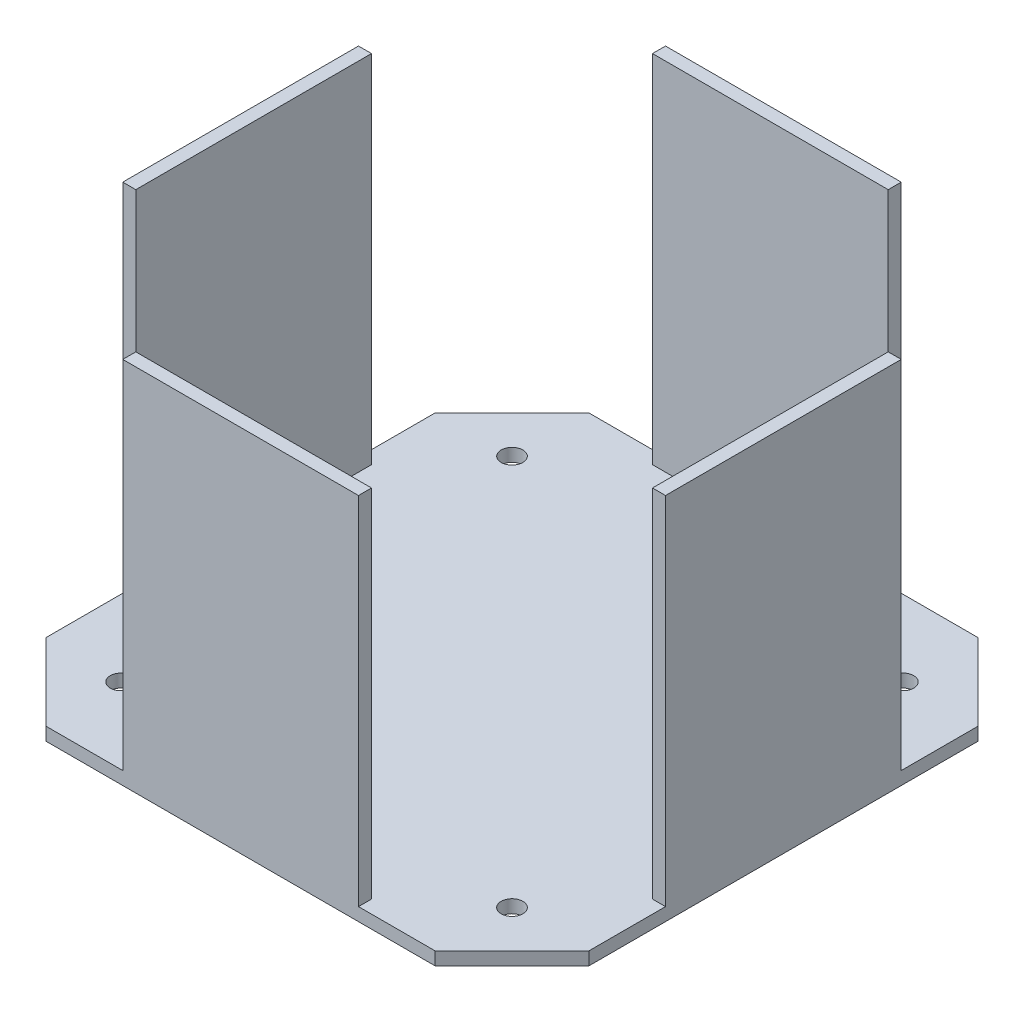
SolidWorks part; units mm, degrees
ref_plane "Front Plane" through (0, 0, 0) normal (0, 0, 1) x (1, 0, 0)
ref_plane "Top Plane" through (0, 0, 0) normal (0, 1, 0) x (1, 0, 0)
ref_plane "Right Plane" through (0, 0, 0) normal (1, 0, 0) x (0, 0, -1)
sketch "Sketch2" plane through (0, 0, 0) normal (0, 1, 0) x (1, 0, 0)
  line L1 (62.5, -62.5) -> (-62.5, -62.5)
  line L2 (62.5, -62.5) -> (62.5, 62.5)
  line L3 (62.5, 62.5) -> (-62.5, 62.5)
  line L4 (-62.5, -62.5) -> (-62.5, 62.5)
  line L5 (62.5, -62.5) -> (-62.5, 62.5) construction
  line L6 (62.5, 62.5) -> (-62.5, -62.5) construction
  point P0 (0, 0)
  dimension "D1" = 125
  dimension "D2" = 125
extrude "Boss-Extrude1" add sketch "Sketch2" along normal blind 85
shell "Shell1" thickness 3 removed face at (0, 85, 0)
sketch "Sketch3" plane through (0, 85, 0) normal (0, 1, 0) x (1, 0, 0)
  line L0 (27.1447, -62.5) -> (62.5, -27.1447) construction
  line L1 (-62.5, -62.5) -> (62.5, -62.5) construction
  line L2 (62.5, -62.5) -> (62.5, 62.5) construction
  line L3 (27.1447, -62.5) -> (62.5, -62.5)
  line L4 (62.5, -62.5) -> (62.5, -27.1447)
  line L5 (27.1447, -62.5) -> (27.1447, -59.5)
  line L6 (-59.5, -59.5) -> (59.5, -59.5) construction
  line L8 (-27.1447, -59.5) -> (-30.1447, -59.5)
  line L9 (62.5, -27.1447) -> (59.5, -27.1447)
  line L10 (59.5, -59.5) -> (59.5, 59.5) construction
  line L11 (59.5, -27.1447) -> (59.5, -30.1447)
  line L13 (59.5, -30.1447) -> (59.5, -59.5)
  line L14 (59.5, -59.5) -> (27.1447, -59.5)
  line L15 (-27.1447, -62.5) -> (-27.1447, -59.5)
  line L16 (-62.5, -62.5) -> (-27.1447, -62.5)
  line L17 (-62.5, -27.1447) -> (-62.5, -62.5)
  line L18 (-62.5, -27.1447) -> (-59.5, -27.1447)
  line L19 (-59.5, -59.5) -> (-59.5, -27.1447)
  line L20 (-30.1447, -59.5) -> (-59.5, -59.5)
  line L21 (-59.5, 27.1447) -> (-59.5, 30.1447)
  line L22 (-62.5, 27.1447) -> (-59.5, 27.1447)
  line L23 (-62.5, 62.5) -> (-62.5, 27.1447)
  line L24 (-27.1447, 62.5) -> (-62.5, 62.5)
  line L25 (-27.1447, 62.5) -> (-27.1447, 59.5)
  line L26 (-59.5, 59.5) -> (-27.1447, 59.5)
  line L27 (-59.5, 30.1447) -> (-59.5, 59.5)
  line L28 (27.1447, 59.5) -> (30.1447, 59.5)
  line L29 (27.1447, 62.5) -> (27.1447, 59.5)
  line L30 (62.5, 62.5) -> (27.1447, 62.5)
  line L31 (62.5, 27.1447) -> (62.5, 62.5)
  line L32 (62.5, 27.1447) -> (59.5, 27.1447)
  line L34 (30.1447, 59.5) -> (59.5, 59.5)
  line L35 (59.5, 59.5) -> (59.5, 27.1447) [skipped]
  line L36 (59.5, 59.5) -> (59.5, 27.1447)
  point P41 (0, 0)
  dimension "D1" = 50
  dimension "D2" = 45
  dimension "D3" = 4
extrude "Cut-Extrude1" cut sketch "Sketch3" against normal up to surface (82 mm away) up to face at (0, 3, 0)
sketch "Sketch4" plane through (0, 3, 0) normal (0, 1, 0) x (1, 0, 0)
  line L0 (-62.5, -44.8223) -> (-62.5, -62.5)
  line L1 (-62.5, -62.5) -> (-62.5, -27.1447) construction
  line L2 (-62.5, -62.5) -> (-44.8223, -62.5)
  line L3 (-27.1447, -62.5) -> (-62.5, -62.5) construction
  line L4 (-44.8223, -62.5) -> (-62.5, -44.8223)
  line L5 (-62.5, 44.8223) -> (-44.8223, 62.5)
  line L6 (-44.8223, 62.5) -> (-62.5, 62.5)
  line L7 (-62.5, 62.5) -> (-62.5, 44.8223)
  line L8 (44.8223, 62.5) -> (62.5, 44.8223)
  line L9 (62.5, 44.8223) -> (62.5, 62.5)
  line L10 (62.5, 62.5) -> (44.8223, 62.5)
  line L11 (62.5, -44.8223) -> (44.8223, -62.5)
  line L12 (44.8223, -62.5) -> (62.5, -62.5)
  line L13 (62.5, -62.5) -> (62.5, -44.8223)
  point P5 (-9.0277, -6.5113)
  point P20 (0, 0)
  dimension "D1" = 4
extrude "Cut-Extrude2" cut sketch "Sketch4" against normal through all
sketch "Sketch5" plane through (0, 3, 0) normal (0, 1, 0) x (1, 0, 0)
  line L0 (62.5, 44.8223) -> (62.5, 27.1447) construction
  circle A0 centre (45.0115, 45.0115) radius 2.5
  circle A1 centre (45.0115, -45.0115) radius 2.5
  circle A2 centre (-45.0115, -45.0115) radius 2.5
  circle A3 centre (-45.0115, 45.0115) radius 2.5
  point P6 (2.1003, 2.38)
  point P15 (0, 0)
  dimension "D1" = 5
  dimension "D2" = 17.4885
  dimension "D3" = 17.4885
  dimension "D4" = 4
extrude "Cut-Extrude3" cut sketch "Sketch5" against normal through all
